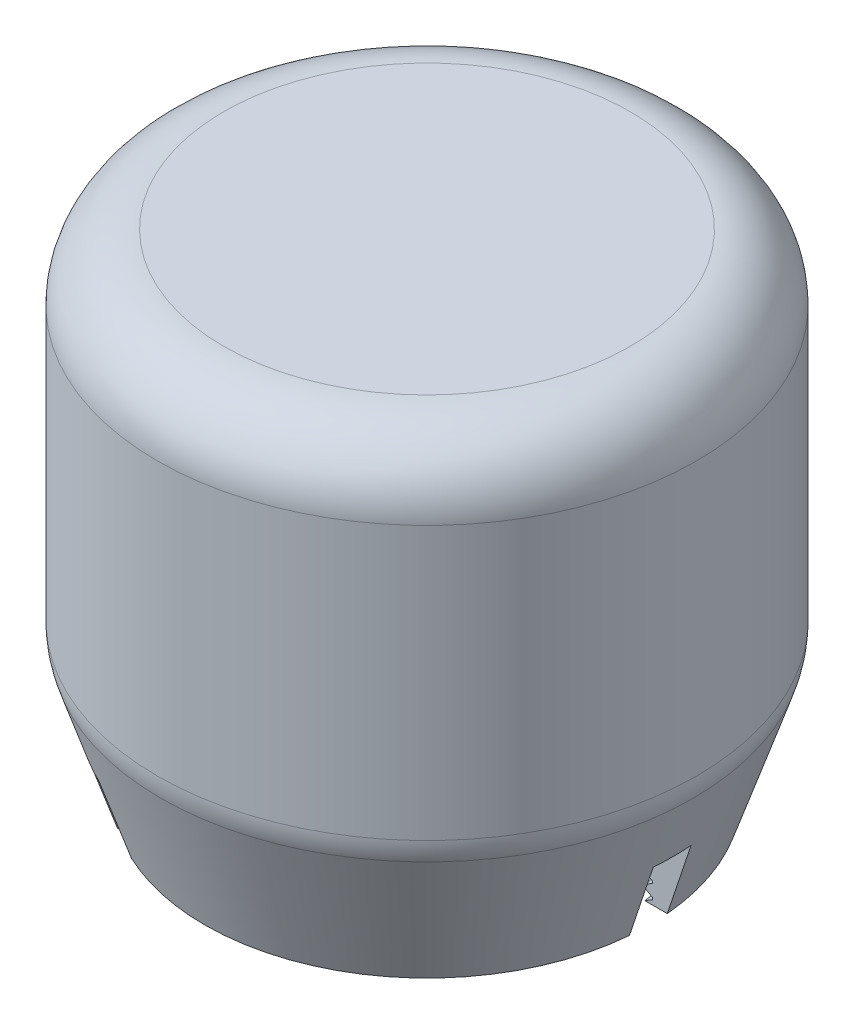
SolidWorks part; units mm, degrees
ref_plane "Front Plane" through (0, 0, 0) normal (0, 0, 1) x (1, 0, 0)
ref_plane "Top Plane" through (0, 0, 0) normal (0, 1, 0) x (1, 0, 0)
ref_plane "Right Plane" through (0, 0, 0) normal (1, 0, 0) x (0, 0, -1)
sketch "Sketch1" plane through (0, 0, 0) normal (0, 1, 0) x (1, 0, 0)
  circle A0 centre (0, 0) radius 26
  circle A1 centre (0, 0) radius 28.5
  dimension "D1" = 52
  dimension "D2" = 2.5
extrude "Boss-Extrude1" add sketch "Sketch1" along normal blind 50
sketch "Sketch2" plane through (0, 50, 0) normal (0, 1, 0) x (1, 0, 0)
  circle A1 centre (0, 0) radius 28.5
  circle A2 centre (0, 0) radius 28.5
  dimension "D1" = 0
extrude "Boss-Extrude2" add sketch "Sketch2" along normal blind 2
sketch "Sketch8" plane through (0, 0, 0) normal (0, -1, 0) x (1, 0, 0)
  circle A0 centre (0, 0) radius 21
  circle A1 centre (0, 0) radius 26 construction
  circle A2 centre (0, 0) radius 26
  dimension "D1" = 42
extrude "Boss-Extrude3" add sketch "Sketch8" against normal blind 10
fillet "Fillet3" radius 5 1 edges at (0, 50, 26)
fillet "Fillet4" radius 7 1 edges at (0, 52, 28.5)
chamfer "Chamfer1" distance 5 angle 45 1 edges at (0, 10, -26)
chamfer "Chamfer2" distance 5 distance2 15 1 edges at (0, 0, 28.5) first distance on face at (0, 0, 28.5)
fillet "Fillet5" radius 7 1 edges at (0, 15, 28.5)
fillet "Fillet6" radius 5 1 edges at (0, 15, -26)
sketch "Sketch9" plane through (0, 0, 0) normal (0, -1, 0) x (1, 0, 0)
  line L0 (0, 2) -> (25.923, 2)
  line L1 (0, -2) -> (25.923, -2)
  line L2 (0, -2) -> (0, 0)
  line L3 (0, 0) -> (0, 2)
  circle A0 centre (0, 0) radius 26 construction
  circle A1 centre (0, 0) radius 26
  circle M5 centre (0, 0) radius 23.5
  circle M6 centre (0, 0) radius 21
  dimension "D1" = 4
sketch "Sketch13" plane through (0, 0, 0) normal (0, 0, 1) x (1, 0, 0)
  line L2 (10.1239, 13.5355) -> (24.5355, 13.5355)
  line L6 (24.5355, 13.5355) -> (16.2247, 5.2247)
  line L7 (16.2247, 5.2247) -> (10.1239, 13.5355)
  line L8 (0, 0) -> (0, 3.6217)
  dimension "D2" = 45
sketch "Sketch19" plane through (0, 0, 0) normal (0, -1, 0) x (1, 0, 0)
  circle A0 centre (0, 0) radius 21.15
  circle A1 centre (0, 0) radius 21 construction
  dimension "D1" = 0.15
extrude "Cut-Extrude3" cut sketch "Sketch19" against normal blind 19
thread "Thread5" pitch 1.5 method cut profile "Thread Profile5" start angle 0, offset 3, length 17, pitch 1.5, diameter 42.3
ref_plane "Plane5" through (21.15, -3, 0) normal (0, 0, 1) x (1, 0, 0)
sketch "Thread Profile5" plane through (21.15, -3, 0) normal (0, 0, 1) x (1, 0, 0)
  line L0 (0, 0) -> (0, 1.5) construction
  line L1 (0, 0) -> (0.8119, 0.4687)
  line L2 (0.8119, 0.4687) -> (0.8119, 0.6562)
  line L3 (0.8119, 0.6562) -> (0, 1.125)
  line L4 (0.8119, 0.5625) -> (0, 0.5625) construction
  line L11 (0, 0) -> (0, 1.125)
  point P2 (0, 0)
  dimension "Pitch" = 1.5
  dimension "Profile_Angle" = 60
  dimension "Profile_Land" = 0.1875
  dimension "Profile_Height" = 0.8119
extrude "Cut-Extrude1" cut sketch "Sketch9" against normal blind 20 contours L1 A1 L0 M5 | L1 L0 M6 M5 | L3 L2 L1 L0 M6 region at (10.4841, 0, 0) region at (22.2199, 0, 0) region at (24.7229, 0, 0)
pattern_circular "CirPattern2" count 3 over 360 about axis through (0, 50, 0) along (0, -1, 0) of "Cut-Extrude1" reverse direction yes
sketch "Sketch20" plane through (0, 0, 0) normal (0, 0, 1) x (1, 0, 0)
  line L0 (-24.5355, 13.5355) -> (-21.6096, 10.6096)
  line L1 (-24.5355, 13.5355) -> (-21.6096, 10.6096) construction
  line L2 (0, 0) -> (0, 23.286)
  line L3 (0, 23.286) -> (-26, 23.286)
  line L4 (-26, 23.286) -> (-26, 17.0711)
  line L5 (-23.5, 0) -> (-28.1408, 13.9223)
  line L6 (-21.1283, 0.7906) -> (-25.7691, 14.7129)
  line L7 (-23.5, 0) -> (-13.4394, 0) construction
  line L8 (-20.0358, 7) -> (0, 7)
  arc A0 (-26, 17.0711) -> (-24.5355, 13.5355) centre (-21, 17.0711) ccw
  arc A1 (-26, 17.0711) -> (-24.5355, 13.5355) centre (-21, 17.0711) ccw construction
  arc A2 (-26, 17.0711) -> (-25.7691, 14.7129) centre (-20.7124, 16.3985) ccw
  arc A3 (-24.1981, 10) -> (-20.0358, 7) centre (-20.0358, 11.3874) ccw
  dimension "D2" = 10
  dimension "D1" = 2.5
  dimension "D3" = 7
revolve "Cut-Revolve3" cut sketch "Sketch20" angle 360 about L2 region at (-12.6099, 15.3305, 0)
